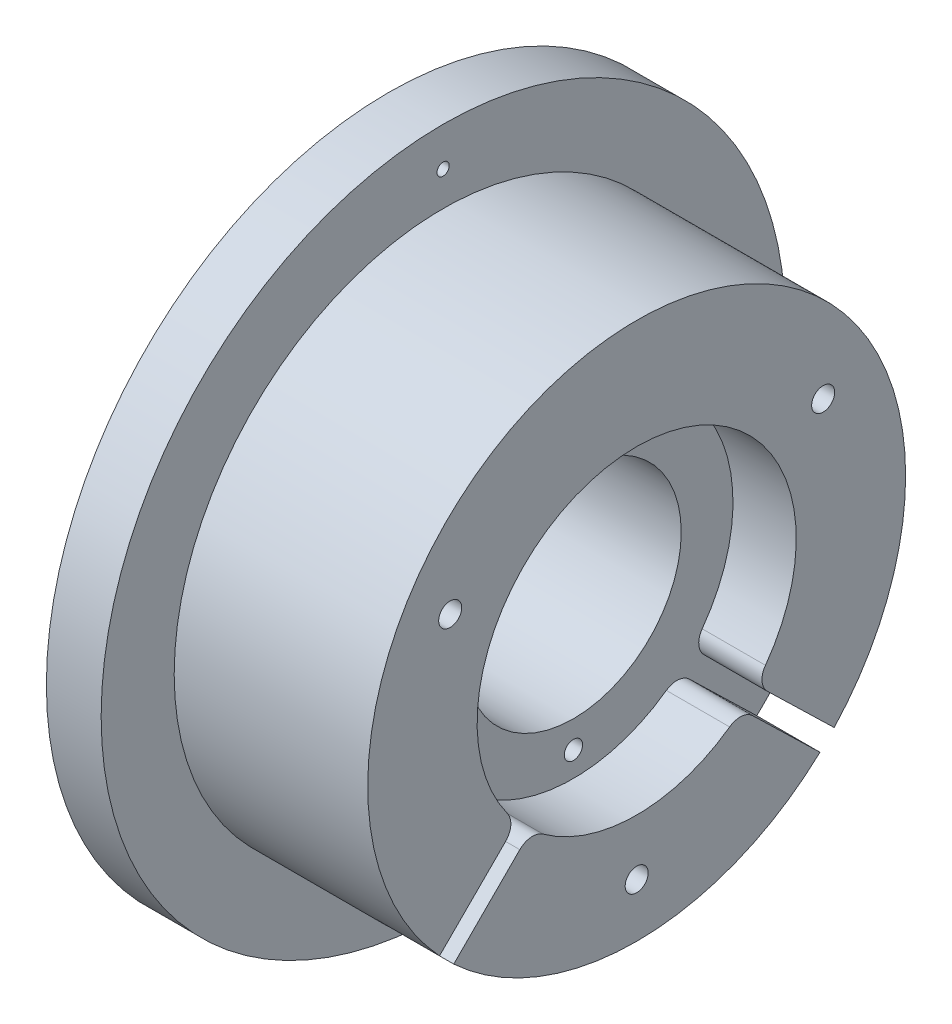
SolidWorks part; units mm, degrees
ref_plane "Front" through (0, 0, 0) normal (0, 0, 1) x (1, 0, 0)
ref_plane "Top" through (0, 0, 0) normal (0, 1, 0) x (1, 0, 0)
ref_plane "Right" through (0, 0, 0) normal (1, 0, 0) x (0, 0, -1)
sketch "Sketch1" plane through (0, 0, 0) normal (0, 0, 1) x (1, 0, 0)
  line L0 (0, 0) -> (0, 23.7871)
  line L1 (0, 23.7871) -> (3.81, 23.7871)
  line L2 (3.81, 23.7871) -> (3.81, 18.7071)
  line L3 (3.81, 18.7071) -> (17.272, 18.7071)
  line L4 (17.272, 18.7071) -> (17.272, 11.1)
  line L5 (17.272, 11.1) -> (12.872, 11.1)
  line L6 (12.872, 11.1) -> (12.872, 0)
  line L7 (12.872, 0) -> (0, 0)
  line L8 (12.872, 7.5) -> (0, 7.5)
  dimension "D1" = 23.7871
  dimension "D2" = 3.81
  dimension "D3" = 13.462
  dimension "D4" = 4.4
  dimension "D5" = 11.1
  dimension "D6" = 18.7071
  dimension "D7" = 7.5
revolve "Revolve1" add sketch "Sketch1" angle 360 about L7 region at (7.4577, 14.209, 0)
sketch "Sketch2" plane through (17.272, 0, 0) normal (1, 0, 0) x (0, 0, -1)
  line L0 (0, 0) -> (-13.2279, -13.2279) construction
  line L1 (0, 0) -> (0, -18.7071) construction
  line L2 (0.3171, 0.3268) -> (13.7426, -12.7005)
  line L3 (-13.7229, -12.7329) -> (-12.7329, -13.7229)
  line L4 (-13.7229, -12.7329) -> (-0.495, 0.495)
  line L5 (-0.495, 0.495) -> (0.495, -0.495)
  line L6 (0.495, -0.495) -> (-12.7329, -13.7229)
  line L7 (12.7677, -13.7053) -> (13.7426, -12.7005)
  line L8 (12.7677, -13.7053) -> (-0.6578, -0.6779)
  line L9 (-0.6578, -0.6779) -> (0.3171, 0.3268)
  circle A0 centre (0, 0) radius 18.7071 construction
  circle A1 centre (-12.9709, 7.4887) radius 0.315
  circle A2 centre (12.9709, 7.4888) radius 0.315
  circle A3 centre (0, 0) radius 18.7071 construction
  circle A4 centre (0, -14.9775) radius 0.315
  point P6 (0, 0)
  point P14 (-13.2279, -13.2279)
  circle M8 centre (0, 0) radius 18.7071
  circle M9 centre (0, 0) radius 11.1
  dimension "D4" = 0.63
  dimension "D1" = 45
  dimension "D2" = 1.4
  dimension "D3" = 14.9775
  dimension "D5" = 3
  dimension "D6" = 2
extrude "Cut-Extrude1" cut sketch "Sketch2" against normal up to surface (4.4 mm away) contours L8 L9 L5 L4 L6 M9 | L6 L4 M9 M8 | L8 L2 M8 M9 | L9 L5 L6 L8 L2 M9 | A4 | A1 | A2 region at (17.272, -4.188, -3.9796) region at (17.272, -10.5487, -10.5196) region at (17.272, -4.068, 4.0898) region at (17.272, -10.5343, 10.5343) region at (17.272, 7.4887, 12.9709) region at (17.272, 7.4888, -12.9709) region at (17.272, -14.9775, 0) up to face at (12.872, 0, -7.5)
sketch "Sketch3" plane through (3.81, 0, 0) normal (1, 0, 0) x (0, 0, -1)
  line L0 (0, 0) -> (0, 21.082) construction
  circle A0 centre (0, 21.082) radius 0.425
  dimension "D1" = 0.85
  dimension "D2" = 21.082
extrude "Cut-Extrude2" cut sketch "Sketch3" against normal through all
sketch "Sketch4" plane through (12.872, 0, 0) normal (1, 0, 0) x (0, 0, -1)
  line L0 (0, -9.375) -> (0, 9.375) construction
  circle A0 centre (0, 9.375) radius 0.635
  circle A1 centre (0, -9.375) radius 0.635
  point P6 (0, 0)
  dimension "D2" = 1.27
  dimension "D1" = 18.75
extrude "Cut-Extrude3" cut sketch "Sketch4" against normal through all
fillet "Fillet1" radius 1.25 4 edges at (15.072, -7.3383, 8.3282) (15.072, -8.3282, 7.3383) (15.072, -8.3798, -7.2794) (15.072, -7.3966, -8.2765)
hole_wizard "M2x0.4 Tapped Hole1" positions "3DSketch2" profile "Sketch5" tap size "M2x0.4" standard "ANSI Metric"
sketch3d "3DSketch2"
  line L0 (12.872, 7.4887, 12.9709) -> (17.272, 7.4887, 12.9709) construction
  line L1 (12.872, 7.4888, -12.9709) -> (17.272, 7.4888, -12.9709) construction
  line L2 (12.872, -14.9775, 0) -> (17.272, -14.9775, 0) construction
  point P0 (17.272, 7.4887, 12.9709)
  point P4 (17.272, 7.4888, -12.9709)
  point P8 (17.272, -14.9775, 0)
sketch "Sketch5" plane through (17.272, 7.4887, 12.9709) normal (0, 1, 0) x (0, 0, -1)
  line L0 (0, 0) -> (0, 7.9807)
  line L1 (0, 7.9807) -> (0.8, 7.5)
  line L2 (0.8, 7.5) -> (0.8, 0)
  line L5 (0.8, 0) -> (0, 0)
  line L10 (0, 7.9807) -> (-0.8, 7.5) construction
  line L11 (0, -6.35) -> (0, 107.95) construction
  dimension "Tap Drill Dia." = 1.6
  dimension "Tap Drill Depth" = 7.5
  dimension "Drill Angle" = 118
cosmetic thread "Hole Thread1" parameters "D1"=4, "D2"=2
cosmetic thread "Hole Thread2" parameters "D1"=4, "D2"=2
cosmetic thread "Hole Thread3" parameters "D1"=4, "D2"=2
